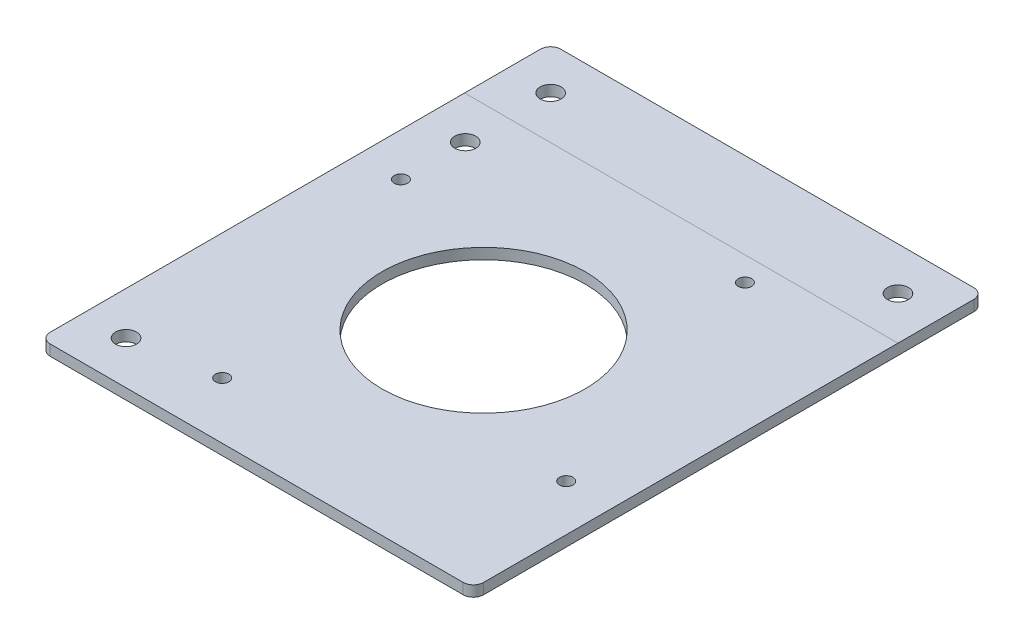
SolidWorks part; units mm, degrees
material "6061-T6 (SS)"
ref_plane "Front Plane" through (0, 0, 0) normal (0, 0, 1) x (1, 0, 0)
ref_plane "Top Plane" through (0, 0, 0) normal (0, 1, 0) x (1, 0, 0)
ref_plane "Right Plane" through (0, 0, 0) normal (1, 0, 0) x (0, 0, -1)
sketch "Sketch1" plane through (0, 0, 0) normal (0, 1, 0) x (1, 0, 0)
  line L0 (29.2285, -585.7621) -> (101.1273, -585.7621) construction
  line L1 (13.1273, -469.9621) -> (141.1273, -469.9621)
  line L3 (13.1273, -620.7621) -> (141.1273, -620.7621)
  line L4 (141.1273, -469.9621) -> (141.1273, -620.7621)
  line L5 (-14.8727, -585.7621) -> (101.1273, -585.7621) construction
  line L6 (101.1273, -585.7621) -> (109.1273, -577.7621) construction
  line L7 (109.1273, -577.7621) -> (109.1273, -528.7621) construction
  line L12 (109.1273, -528.7621) -> (101.1273, -520.7621) construction
  line L13 (101.1273, -520.7621) -> (-15.8395, -520.7621) construction
  line L14 (101.1273, -520.7621) -> (-14.8727, -520.7621) construction
  line L16 (25.8273, -482.6621) -> (13.1273, -482.6621) construction
  line L17 (25.8273, -482.6621) -> (25.8273, -469.9621) construction
  line L18 (128.4273, -482.6621) -> (128.4273, -469.9621) construction
  line L19 (128.4273, -482.6621) -> (141.1273, -482.6621) construction
  line L20 (25.8273, -608.0621) -> (13.1273, -608.0621) construction
  line L21 (25.8273, -608.0621) -> (25.8273, -604.9621) construction
  line L22 (25.8273, -608.0621) -> (25.8273, -620.7621) construction
  line L23 (25.8273, -482.6621) -> (28.9273, -482.6621) construction
  line L24 (13.1273, -531.2621) -> (29.3273, -531.2621) construction
  line L25 (128.4273, -482.6621) -> (128.4273, -485.7621) construction
  line L30 (13.1273, -469.9621) -> (13.1273, -620.7621)
  line L31 (29.3273, -531.2621) -> (-12.8727, -531.2621) construction
  line L32 (25.8273, -482.6621) -> (25.8273, -507.8621) construction
  line L35 (-12.8727, -535.2621) -> (29.3273, -535.2621) construction
  line L36 (13.1273, -535.2621) -> (29.3273, -535.2621) construction
  line L37 (25.8273, -507.8621) -> (28.9273, -507.8621) construction
  circle A0 centre (76.6273, -553.2621) radius 30
  circle A1 centre (25.8273, -482.6621) radius 3.1
  circle A2 centre (128.4273, -482.6621) radius 3.1
  circle A4 centre (25.8273, -608.0621) radius 3.1
  arc A5 (29.3273, -535.2621) -> (29.3273, -531.2621) centre (29.3273, -533.2621) ccw construction
  circle A6 centre (25.8273, -507.8621) radius 3.1
  dimension "D4" = 60
  dimension "D5" = 88
  dimension "D6" = 6.2
  dimension "D1" = 50.8
  dimension "D2" = 35
  dimension "D3" = 32
  dimension "D7" = 12.7
  dimension "D8" = 25.2
extrude "Boss-Extrude1" add sketch "Sketch1" along normal blind 3.175
fillet "Fillet1" radius 3 4 edges at (141.1273, 1.5875, 469.9621) (141.1273, 1.5875, 620.7621) (13.1273, 1.5875, 620.7621) (13.1273, 1.5875, 469.9621)
sketch "Sketch3" plane through (0, 3.175, 0) normal (0, 1, 0) x (1, 0, 0)
  line L0 (25.8273, -482.6621) -> (25.8273, -608.0621) construction
  line L1 (25.8273, -526.8685) -> (103.0209, -502.4621) construction
  line L2 (25.8273, -526.8685) -> (50.2338, -604.0621) construction
  line L3 (50.2338, -604.0621) -> (127.4273, -579.6556) construction
  line L4 (103.0209, -502.4621) -> (127.4273, -579.6556) construction
  line L5 (25.8273, -526.8685) -> (127.4273, -579.6556) construction
  line L6 (50.2338, -604.0621) -> (103.0209, -502.4621) construction
  line L7 (12.8763, -520.1397) -> (109.7497, -489.5111) construction
  line L8 (12.8763, -520.1397) -> (43.505, -617.013) construction
  line L9 (43.505, -617.013) -> (140.3783, -586.3844) construction
  line L10 (109.7497, -489.5111) -> (140.3783, -586.3844) construction
  circle A0 centre (25.8273, -526.8685) radius 1.985
  circle A1 centre (76.6273, -553.2621) radius 30 construction
  circle A2 centre (103.0209, -502.4621) radius 1.985
  circle A3 centre (127.4273, -579.6556) radius 1.985
  circle A4 centre (50.2338, -604.0621) radius 1.985
  point P4 (76.6273, -553.2621)
  point P23 (76.6273, -553.2621)
  dimension "D5" = 3.97
  dimension "D1" = 80.96
  dimension "D2" = 101.6
  dimension "D3" = 90
  dimension "D4" = 90
  dimension "D6" = 4
extrude "Cut-Extrude1" cut sketch "Sketch3" against normal through all
sketch "Sketch4" plane through (0, 3.175, 0) normal (0, 1, 0) x (1, 0, 0)
  line L0 (138.1273, -469.9621) -> (16.1273, -469.9621) construction
  line L4 (13.1273, -495.3621) -> (141.1273, -495.3621)
  line L9 (13.1273, -495.3621) -> (13.1273, -469.9621)
  line L10 (13.1273, -469.9621) -> (141.1273, -469.9621)
  line L11 (141.1273, -495.3621) -> (141.1273, -469.9621)
  line L12 (13.1273, -495.3621) -> (141.1273, -469.9621) construction
  line L13 (13.1273, -469.9621) -> (141.1273, -495.3621) construction
  line L14 (13.1273, -472.9621) -> (13.1273, -617.7621) construction
  point P4 (77.1273, -482.6621)
  dimension "D1" = 25.4
  dimension "D2" = 128
split line "Split Line2"
